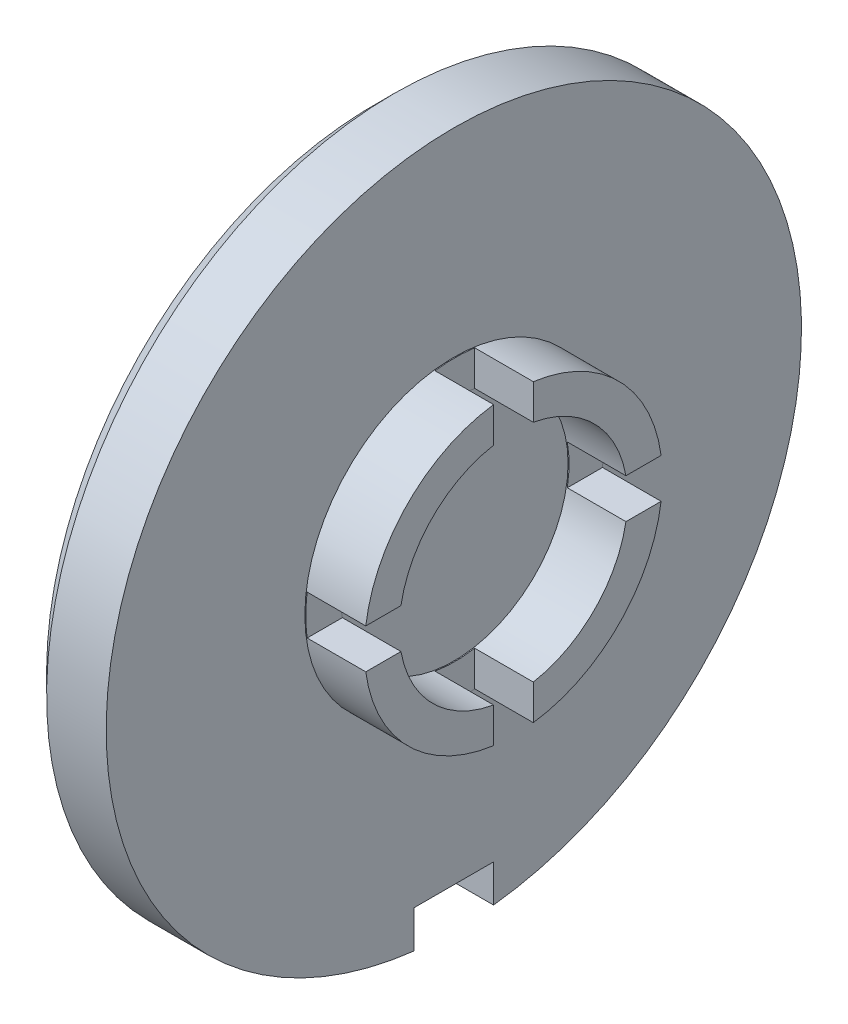
SolidWorks part; units mm, degrees
ref_plane "Front Plane" through (0, 0, 0) normal (0, 0, 1) x (1, 0, 0)
ref_plane "Top Plane" through (0, 0, 0) normal (0, 1, 0) x (1, 0, 0)
ref_plane "Right Plane" through (0, 0, 0) normal (1, 0, 0) x (0, 0, -1)
ref_plane "Plane1" through (0, 0, -52) normal (0, 0, 1) x (1, 0, 0)
sketch "Sketch1" plane through (0, 0, -52) normal (0, 0, 1) x (1, 0, 0)
  line L0 (-90.6, -65) -> (-77.8, -65) construction
  line L1 (-82.8, -62.7) -> (-84, -62.7)
  line L2 (-84, -62.7) -> (-84, -65)
  line L3 (-84, -65) -> (-85.6, -65)
  line L4 (-85.6, -65) -> (-85.6, -58.4)
  line L5 (-85.6, -58.4) -> (-85.2, -58)
  line L6 (-85.2, -58) -> (-84, -58)
  line L7 (-84, -58) -> (-84, -62)
  line L8 (-84, -62) -> (-82.8, -62)
  line L9 (-82.8, -62) -> (-82.8, -62.7)
revolve "Revolve1" add sketch "Sketch1" angle 360 about L0
sketch "Sketch2" plane through (0, 0, 0) normal (0, 0, 1) x (1, 0, 0)
  line L1 (-83.98, -65.4) -> (-82.7, -65.4)
  line L2 (-83.98, -65.4) -> (-83.98, -64.6)
  line L3 (-83.98, -64.6) -> (-82.7, -64.6)
  line L4 (-82.7, -65.4) -> (-82.7, -64.6)
extrude "Boss-Extrude1" add sketch "Sketch2" along normal blind 6.4 from offset 55.2 separate body offset against normal yes
combine bodies "Combine1" operation type subtract main body 101 bodies to subtract 102
sketch "Sketch3" plane through (0, 0, 0) normal (0, 0, 1) x (1, 0, 0)
  line L1 (-83.98, -68.2) -> (-82.7, -68.2)
  line L2 (-83.98, -68.2) -> (-83.98, -61.8)
  line L3 (-83.98, -61.8) -> (-82.7, -61.8)
  line L4 (-82.7, -68.2) -> (-82.7, -61.8)
extrude "Boss-Extrude2" add sketch "Sketch3" along normal blind 0.8 from offset 52.4 separate body offset against normal yes
combine bodies "Combine2" operation type subtract main body 103 bodies to subtract 104
sketch "Sketch4" plane through (0, 0, 0) normal (0, 0, 1) x (1, 0, 0)
  line L1 (-85.7, -72.1) -> (-83.9, -72.1)
  line L2 (-85.7, -72.1) -> (-85.7, -71.2)
  line L3 (-85.7, -71.2) -> (-83.9, -71.2)
  line L4 (-83.9, -72.1) -> (-83.9, -71.2)
extrude "Boss-Extrude3" add sketch "Sketch4" along normal blind 1.6 from offset 52.8 separate body offset against normal yes
combine bodies "Combine3" operation type subtract main body 105 bodies to subtract 106
